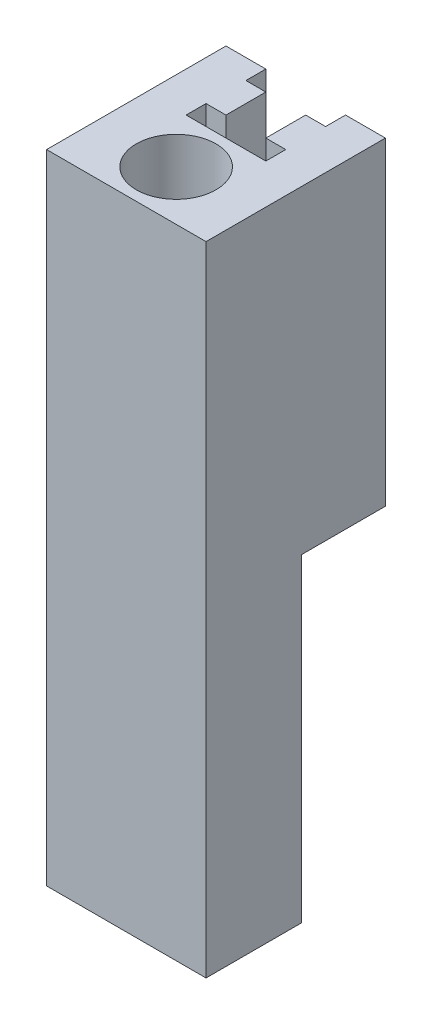
SolidWorks part; units mm, degrees
ref_plane "Front Plane" through (0, 0, 0) normal (0, 0, 1) x (1, 0, 0)
ref_plane "Top Plane" through (0, 0, 0) normal (0, 1, 0) x (1, 0, 0)
ref_plane "Right Plane" through (0, 0, 0) normal (1, 0, 0) x (0, 0, -1)
sketch "Sketch1" plane through (0, 0, 0) normal (0, 1, 0) x (1, 0, 0)
  line L0 (10, 0) -> (-10, 0) construction
  line L1 (-10, 0) -> (-20, 0)
  line L2 (-20, 0) -> (-20, -45)
  line L3 (-20, -45) -> (20, -45)
  line L4 (20, -45) -> (20, 0)
  line L5 (20, 0) -> (10, 0)
  line L6 (10, 0) -> (10, -5)
  line L7 (10, -5) -> (5, -5)
  line L8 (5, -5) -> (5, -15)
  line L9 (5, -15) -> (10, -15)
  line L10 (10, -15) -> (10, -20)
  line L11 (10, -20) -> (-10, -20)
  line L12 (0, 0) -> (0, -20) construction
  line L13 (-10, 0) -> (-10, -5)
  line L14 (-10, -5) -> (-5, -5)
  line L15 (-5, -5) -> (-5, -15)
  line L16 (-5, -15) -> (-10, -15)
  line L17 (-10, -15) -> (-10, -20)
  line L18 (0, -20) -> (0, -45) construction
  circle A1 centre (0, -32.5) radius 10
  point P3 (0, 0)
  point P22 (-0.0661, -45)
  dimension "D10" = 20
  dimension "D1" = 45
  dimension "D2" = 5
  dimension "D3" = 5
  dimension "D4" = 5
  dimension "D5" = 10
  dimension "D6" = 5
  dimension "D7" = 10
  dimension "D8" = 40
  dimension "D9" = 20
  dimension "D11" = 32.5
  dimension "D12" = 20
extrude "Boss-Extrude1" add sketch "Sketch1" against normal blind 160
sketch "Sketch2" plane through (0, -160, 0) normal (0, -1, 0) x (1, 0, 0)
  line L0 (-20, 0) -> (-20, 45) construction
  line L1 (20, 0) -> (-20, 0)
  line L2 (20, 0) -> (20, 21)
  line L3 (20, 21) -> (-20, 21)
  line L4 (-20, 0) -> (-20, 21)
  dimension "D1" = 21
extrude "Cut-Extrude1" cut sketch "Sketch2" against normal blind 80
sketch "Sketch3" plane through (20, 0, 0) normal (1, 0, 0) x (0, 0, -1)
  line L0 (0, -80) -> (0, 0) construction
  line L1 (0, 0) -> (-20, 0)
  line L2 (0, 0) -> (0, -25)
  line L3 (0, -25) -> (-20, -25)
  line L4 (-20, 0) -> (-20, -25)
  line L5 (-20, -25) -> (0, -25)
  line L6 (-20, -25) -> (-20, -35)
  line L7 (-20, -35) -> (0, -35)
  line L8 (0, -25) -> (0, -35)
  dimension "D1" = 20
  dimension "D2" = 25
  dimension "D3" = 10
